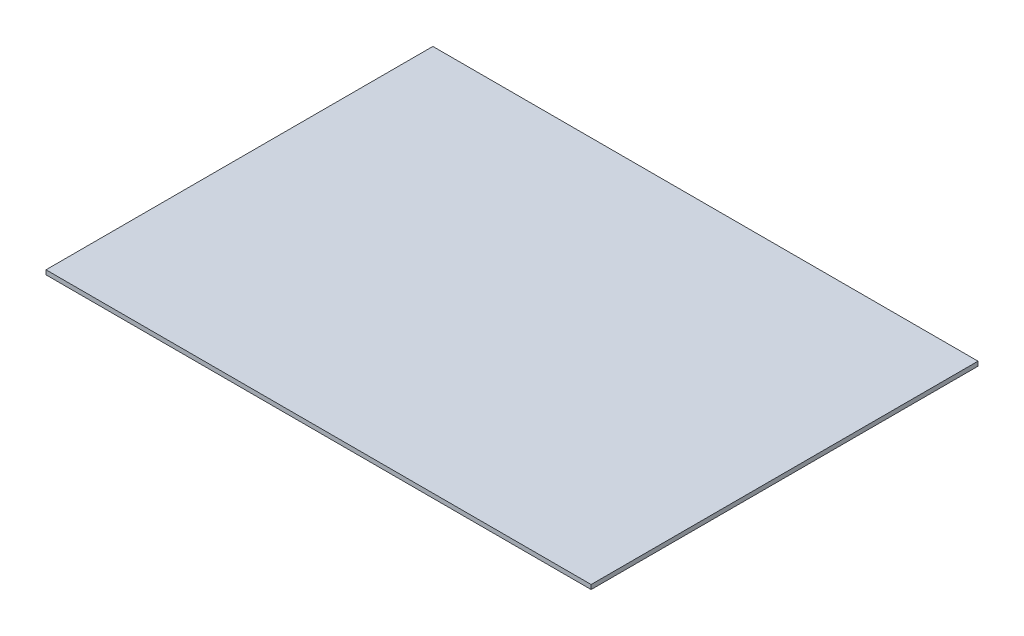
SolidWorks part; units mm, degrees
ref_plane "Front Plane" through (0, 0, 0) normal (0, 0, 1) x (1, 0, 0)
ref_plane "Top Plane" through (0, 0, 0) normal (0, 1, 0) x (1, 0, 0)
ref_plane "Right Plane" through (0, 0, 0) normal (1, 0, 0) x (0, 0, -1)
sketch "Sketch1" plane through (0, 0, 0) normal (0, 1, 0) x (1, 0, 0)
  line L1 (0, 0) -> (393.7, 0)
  line L2 (0, 0) -> (0, 279.4)
  line L3 (0, 279.4) -> (393.7, 279.4)
  line L4 (393.7, 0) -> (393.7, 279.4)
  dimension "D1" = 393.7
  dimension "D2" = 279.4
extrude "Boss-Extrude1" add sketch "Sketch1" along normal blind 3.175
